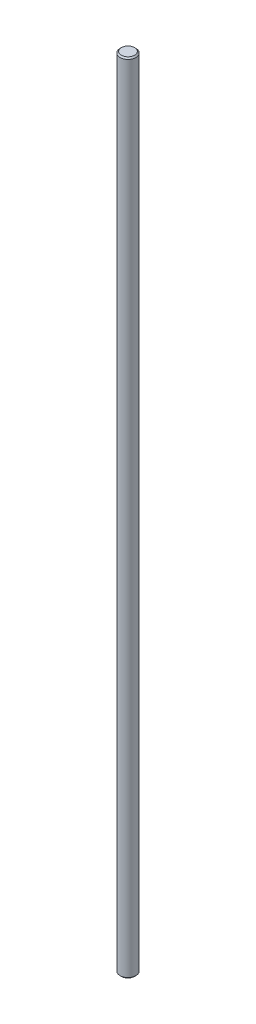
SolidWorks part; units mm, degrees
ref_plane "Front Plane" through (0, 0, 0) normal (0, 0, 1) x (1, 0, 0)
ref_plane "Top Plane" through (0, 0, 0) normal (0, 1, 0) x (1, 0, 0)
ref_plane "Right Plane" through (0, 0, 0) normal (1, 0, 0) x (0, 0, -1)
sketch "Sketch1" plane through (0, 0, 0) normal (0, 1, 0) x (1, 0, 0)
  circle A0 centre (0, 0) radius 3
  dimension "D1" = 6
extrude "Boss-Extrude1" add sketch "Sketch1" along normal blind 301
chamfer "Chamfer1" distance 0.5 angle 45 1 edges at (0, 0, 3)
chamfer "Chamfer2" distance 0.5 angle 45 1 edges at (0, 301, 3)
sketch "Sketch2" plane through (0, 0, 0) normal (0, -1, 0) x (1, 0, 0)
  circle A0 centre (0, 0) radius 3 construction
  circle A1 centre (0, 0) radius 3
curve "Helix/Spiral1" [suppressed] pitch 0.7 height 155 turns 221.4286
sketch "Sketch3" [suppressed] plane through (0, 0, 0) normal (1, 0, 0) x (0, 0, -1)
  line L0 (2, 0) -> (1.4696, 0) construction
  line L1 (1.6211, -0.0875) -> (2.2652, -0.4594)
  line L2 (2.2652, -0.4594) -> (2.2652, 0.4594)
  line L3 (2.2652, 0.4594) -> (1.6211, 0.0875)
  line L4 (-1.5, 0) -> (1.5, 0) construction
  circle A0 centre (2, 0) radius 0.2652 construction
  arc A1 (1.6211, 0.0875) -> (1.6211, -0.0875) centre (1.6716, 0) ccw
  point P7 (1.6211, 0)
  dimension "D1" = 0.5304
  dimension "D2" = 0.1515
sweep "Cut-Sweep1" [suppressed] cut profiles "Sketch3" path "Helix/Spiral1"
